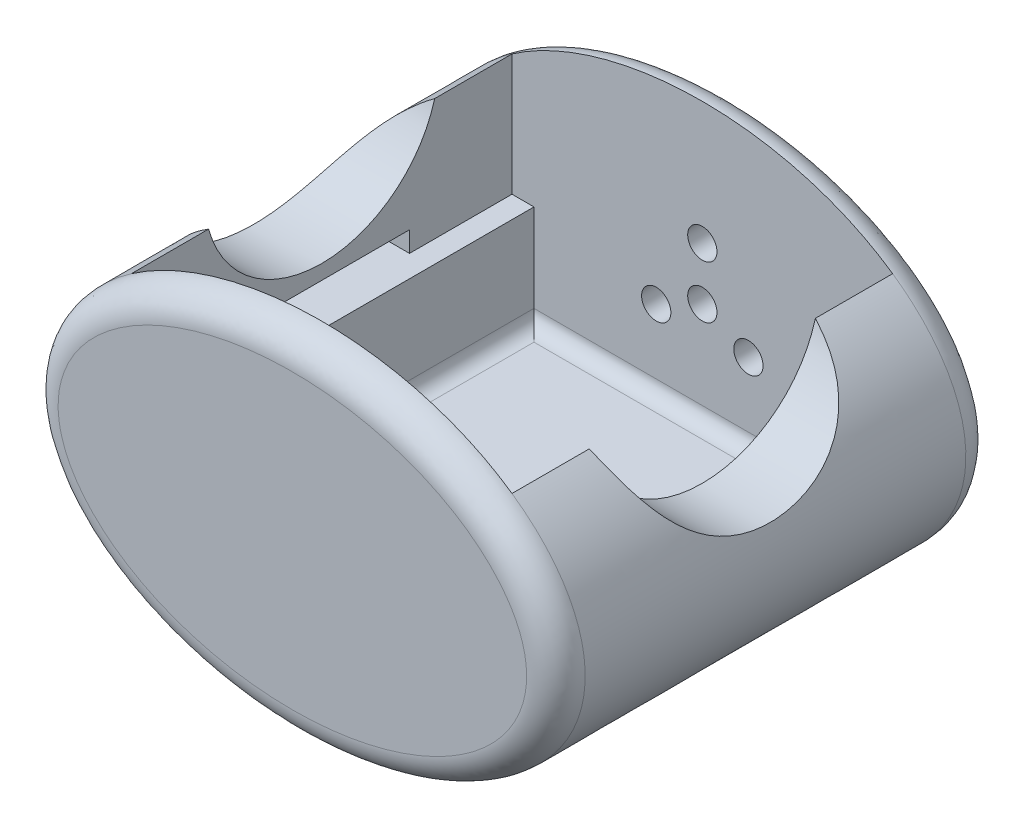
SolidWorks part; units mm, degrees
ref_plane "Front Plane" through (0, 0, 0) normal (0, 0, 1) x (1, 0, 0)
ref_plane "Top Plane" through (0, 0, 0) normal (0, 1, 0) x (1, 0, 0)
ref_plane "Right Plane" through (0, 0, 0) normal (1, 0, 0) x (0, 0, -1)
sketch "Sketch1" plane through (0, 0, 0) normal (0, 0, 1) x (1, 0, 0)
  ellipse E0 centre (0, 0) end of major axis (-22.86, 0) minor radius 15.24
extrude "Boss-Extrude4" add sketch "Sketch1" along normal blind 45.72 contours E0
sketch "Sketch4" plane through (0, 0, 45.72) normal (0, 0, 1) x (1, 0, 0)
  line L1 (14.605, -8.89) -> (-14.605, -8.89)
  line L2 (14.605, -8.89) -> (14.605, 8.89)
  line L3 (14.605, 8.89) -> (-14.605, 8.89)
  line L4 (-14.605, -8.89) -> (-14.605, 8.89)
  dimension "D1" = 8.89
  dimension "D2" = 17.78
  dimension "D3" = 14.605
  dimension "D4" = 29.21
extrude "Cut-Extrude2" cut sketch "Sketch4" against normal blind 33.02 from offset 10.16 offset against normal yes
sketch "Sketch7" plane through (0, 0, 0) normal (1, 0, 0) x (0, 0, -1)
  line L0 (-45.72, 15.24) -> (-45.72, -15.24) construction
  line L1 (-38.1, 16.1024) -> (-52.7439, 16.1024)
  line L2 (-38.1, 16.1024) -> (-38.1, -19.4576)
  line L3 (-38.1, -19.4576) -> (-52.7439, -19.4576)
  line L4 (-52.7439, 16.1024) -> (-52.7439, -19.4576)
  dimension "D1" = 7.62
  dimension "D2" = 14.6439
  dimension "D3" = 35.56
extrude "Cut-Extrude4" cut sketch "Sketch7" against normal blind 33.02 and the other way blind 33.02
sketch "Sketch8" plane through (0, 0, 0) normal (0, 0, 1) x (1, 0, 0)
  circle A0 centre (0, 0) radius 1.27
  circle A1 centre (3.9984, -1.9992) radius 1.27
  circle A2 centre (-3.9984, -1.9992) radius 1.27
  circle A3 centre (0, 4.572) radius 1.27
  dimension "D1" = 4.4704
  dimension "D2" = 2.54
  dimension "D3" = 2.54
  dimension "D4" = 2.54
  dimension "D5" = 2.54
  dimension "D7" = 4.572
  dimension "D8" = 4.4704
extrude "Cut-Extrude5" cut sketch "Sketch8" along normal blind 2.54
fillet "Fillet1" radius 2.54 1 edges at (-22.86, 0, 0)
fillet "Fillet2" radius 2.54 1 edges at (-22.86, 0, 38.1)
sketch "Sketch12" plane through (0, 0, 0) normal (0, 0, -1) x (-1, 0, 0)
  line L1 (-16.51, 0) -> (16.51, 0)
  line L2 (-16.51, 0) -> (-16.51, 19.05)
  line L3 (-16.51, 19.05) -> (16.51, 19.05)
  line L4 (16.51, 0) -> (16.51, 19.05)
  dimension "D1" = 33.02
  dimension "D2" = 19.05
  dimension "D3" = 19.05
  dimension "D4" = 16.51
fillet "Fillet3" radius 1.27 4 edges at (-14.605, -8.89, 19.05) (0, -8.89, 2.54) (14.605, -8.89, 19.05) (0, -8.89, 35.56)
sketch "Sketch13" plane through (0, -8.89, 0) normal (0, 1, 0) x (1, 0, 0)
  line L0 (14.605, -35.56) -> (-14.605, -35.56) construction
  line L1 (-2.54, -20.828) -> (2.54, -20.828)
  line L2 (-2.54, -20.828) -> (-2.54, -15.748)
  line L3 (-2.54, -15.748) -> (2.54, -15.748)
  line L4 (2.54, -20.828) -> (2.54, -15.748)
  dimension "D1" = 5.08
  dimension "D2" = 5.08
  dimension "D3" = 2.54
  dimension "D4" = 14.732
extrude "Cut-Extrude13" cut sketch "Sketch13" against normal through all from offset 2.54 offset against normal yes
sketch "Sketch14" plane through (0, -11.43, 0) normal (0, -1, 0) x (1, 0, 0)
  line L0 (-2.54, 20.828) -> (2.54, 20.828) construction
  line L1 (2.54, 20.828) -> (2.54, 15.748) construction
  line L2 (2.54, 15.748) -> (-2.54, 15.748) construction
  circle A0 centre (0, 20.078) radius 0.5
  circle A1 centre (0, 16.498) radius 0.5
  dimension "D1" = 1
  dimension "D4" = 1
  dimension "D2" = 0.75
  dimension "D3" = 2.54
  dimension "D5" = 0.75
  dimension "D6" = 2.54
extrude "Cut-Extrude14" cut sketch "Sketch14" against normal through all both and the other way through all
extrude "Cut-Extrude16" cut sketch "Sketch12" against normal blind 33.02 from offset 2.54 offset against normal yes
sketch "Sketch17" plane through (16.51, 0, 0) normal (-1, 0, 0) x (0, 0, 1)
  line L0 (35.56, 0) -> (2.54, 0) construction
  line L1 (11.43, 0) -> (26.67, 0)
  line L2 (11.43, 0) -> (11.43, 1.778)
  line L3 (11.43, 1.778) -> (26.67, 1.778)
  line L4 (26.67, 0) -> (26.67, 1.778)
  line L5 (2.54, 10.5409) -> (2.54, 15.24) construction
  dimension "D1" = 1.778
  dimension "D2" = 15.24
  dimension "D3" = 8.89
extrude "Cut-Extrude17" cut sketch "Sketch17" against normal blind 1.778
sketch "Sketch18" plane through (-16.51, 0, 0) normal (1, 0, 0) x (0, 0, -1)
  line L0 (-35.56, 0) -> (-2.54, 0) construction
  line L1 (-26.67, 0) -> (-11.43, 0)
  line L2 (-26.67, 0) -> (-26.67, 1.778)
  line L3 (-26.67, 1.778) -> (-11.43, 1.778)
  line L4 (-11.43, 0) -> (-11.43, 1.778)
  line L5 (-35.56, 10.5409) -> (-35.56, 15.24) construction
  dimension "D1" = 15.24
  dimension "D2" = 8.89
  dimension "D3" = 1.778
extrude "Cut-Extrude18" cut sketch "Sketch18" against normal blind 1.778
sketch "Sketch19" plane through (0, 0, 0) normal (1, 0, 0) x (0, 0, -1)
  line L0 (-35.56, 10.5409) -> (-35.56, -15.24) construction
  line L2 (-26.67, 1.778) -> (-11.43, 1.778) construction
  circle A0 centre (-19.05, 13.208) radius 10.16
  dimension "D1" = 20.32
  dimension "D2" = 16.51
  dimension "D3" = 11.43
extrude "Cut-Extrude19" cut sketch "Sketch19" against normal through all both and the other way through all
